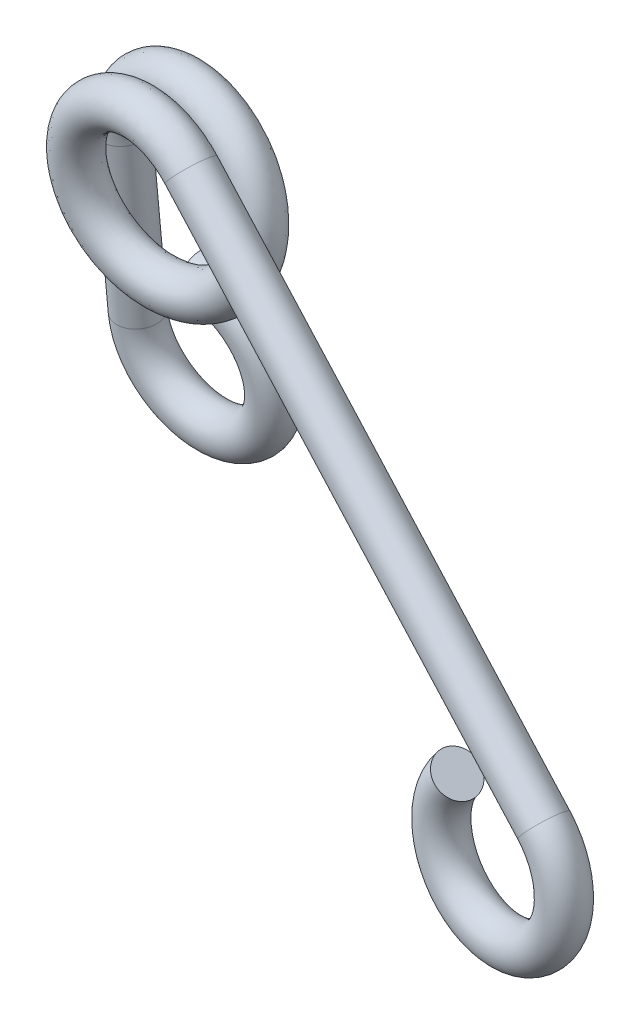
SolidWorks part; units mm, degrees
note: '?' marks a value the reader was unsure of.
ref_plane "Front Plane" through (0, 0, 0) normal (0, 0, 1) x (1, 0, 0)
ref_plane "Top Plane" through (0, 0, 0) normal (0, 1, 0) x (1, 0, 0)
ref_plane "Right Plane" through (0, 0, 0) normal (1, 0, 0) x (0, 0, -1)
sketch "Sketch1" plane through (0, 0, 0) normal (0, 0, 1) x (1, 0, 0)
  circle A0 centre (0, 0) radius 2.925
  dimension "D1" = 5.85
curve "Helix/Spiral1" pitch 1.6911 height 2.304 turns 1.3624
sweep "Sweep1" add path "Helix/Spiral1" circular profile diameter 1.537 parameters "D3"=1.537
sketch "Sketch7" plane through (0, 0, 0) normal (0, -0.9958, -0.0916) x (1, 0, 0)
  line L0 (-3.6935, 0) -> (-2.1565, 0) construction
  circle A0 centre (-2.925, 0) radius 0.7685 construction
  circle A1 centre (-2.925, 0) radius 0.7685
extrude "Boss-Extrude1" add sketch "Sketch7" along normal blind 6.112
sketch "Sketch8" plane through (0.1599, -0.1365, 0.0193) normal (0.7575, -0.6464, 0.0916) x (0.0959, -0.0286, -0.995)
  line L0 (-2.1742, 2.2471) -> (-2.1742, 3.7841) construction
  circle A0 centre (-2.1742, 3.0156) radius 0.7685 construction
  circle A1 centre (-2.1742, 3.0156) radius 0.7685
extrude "Boss-Extrude2" add sketch "Sketch8" along normal blind 19.442
ref_axis "Axis1" through (-2.925, -6.2259, -0.5729) along (0, 0.9958, 0.0916)?
ref_plane "Plane1" through (0, 0, 0) normal (0, -0.0916, 0.9958) x (1, 0, 0)
ref_axis "Axis2" through (10.5191, -5.131, 3.3471) along (-0.7575, 0.6464, -0.0916)?
ref_plane "Plane2" through (-0.2086, 0.0622, 2.1633) normal (0.0959, -0.0286, -0.995) x (-0.9954, -0.002, -0.0959)
sketch "Sketch10" plane through (0, 0, 0) normal (0, -0.0916, 0.9958) x (1, 0, 0)
  line L0 (-3.6935, -6.112) -> (-2.1565, -6.112) construction
  line L1 (-3.6935, -6.112) -> (-2.1565, -6.112) construction
  line L2 (-2.925, -6.112) -> (-0.425, -6.112) construction
  line L3 (-0.425, -6.112) -> (-0.425, -3.612) construction
  line L4 (-2.925, -6.2522) -> (-2.925, 0.1402) construction
  arc A0 (-2.925, -6.112) -> (-0.425, -3.612) centre (-0.425, -6.112) ccw
  dimension "D2" = 2.5
  dimension "D1" = 90
sketch "Sketch11" plane through (0, -6.0863, -0.56) normal (0, -0.9958, -0.0916) x (1, 0, 0)
  circle A0 centre (-2.925, 0) radius 0.7685 construction
  circle A1 centre (-2.925, 0) radius 0.7685
sweep "Sweep2" add profiles "Sketch11" path "Sketch10"
sketch "Sketch12" plane through (-0.2086, 0.0622, 2.1633) normal (0.0959, -0.0286, -0.995) x (-0.9954, -0.002, -0.0959)
  line L0 (-17.4181, -9.8578) -> (-16.4218, -11.0282) construction
  line L1 (-17.4181, -9.8578) -> (-16.4218, -11.0282) construction
  line L2 (-16.9199, -10.443) -> (-15.2994, -12.3466) construction
  line L3 (-15.2994, -12.3466) -> (-13.3957, -10.7261) construction
  line L4 (-10.7812, -5.2174) -> (-8.2376, -3.0521) construction
  arc A0 (-16.9199, -10.443) -> (-13.3957, -10.7261) centre (-15.2994, -12.3466) ccw
  dimension "D2" = 2.5
  dimension "D1" = 90
sketch "Sketch13" plane through (14.8871, -12.7035, 1.8008) normal (0.7575, -0.6464, 0.0916) x (0.0959, -0.0286, -0.995)
  circle A0 centre (-2.1742, 3.0156) radius 0.7685 construction
  circle A1 centre (-2.1742, 3.0156) radius 0.7685
sweep "Sweep3" add profiles "Sketch13" path "Sketch12"
equation "\"D_coil\"=0.005850"
equation "\"d_wire\"=0.001537"
equation "\"Nb\"=1.362432"
equation "\"loop_diam\"=0.005000"
equation "\"height\"=0.002304"
equation "\"D1@Sketch1\"=\"D_coil\"*1000"
equation "\"D3@Helix/Spiral1\"=\"height\"*1000"
equation "\"D5@Helix/Spiral1\"=\"Nb\""
equation "\"D3@Sweep1\"=\"d_wire\"*1000"
equation "\"D1@Boss-Extrude1\" = \"l_s_arm\" * 1000"
equation "\"D1@Boss-Extrude2\"= \"l_a_arm\" * 1000"
equation "\"D2@Sketch10\"=\"loop_diam\"*1000/2"
equation "\"D1@Sketch12\"=90"
equation "\"D2@Sketch12\"=\"loop_diam\"*1000/2"
equation "\"l_s_arm\"=0.006112"
equation "\"l_a_arm\"=0.019442"
